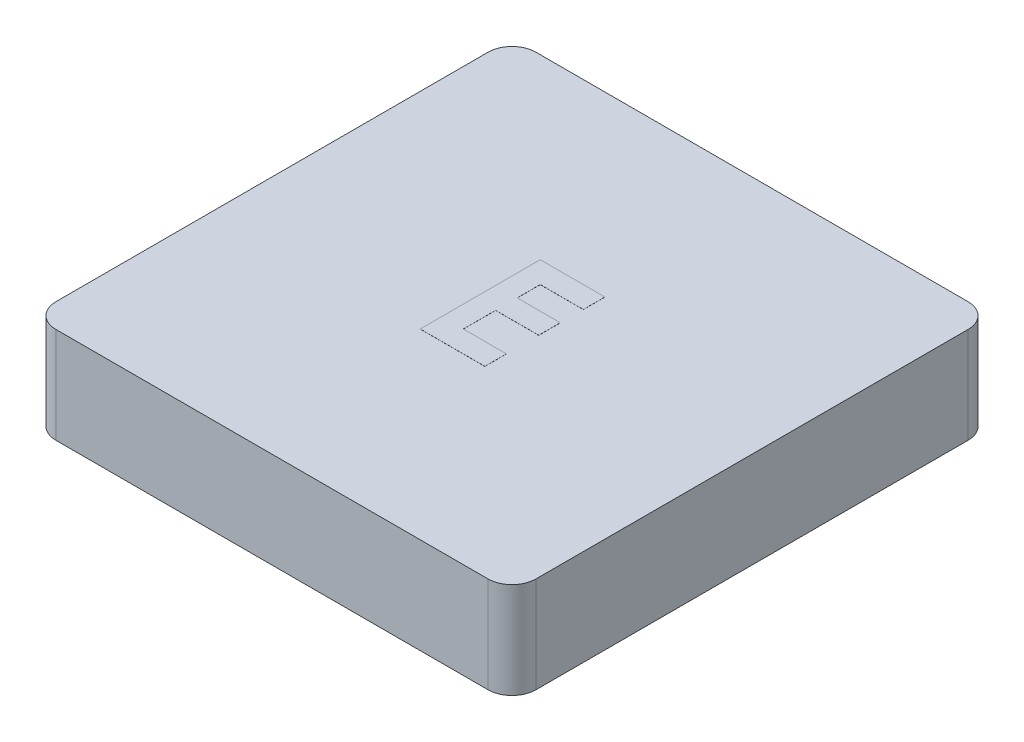
SolidWorks part; units mm, degrees
ref_plane "Front Plane" through (0, 0, 0) normal (0, 0, 1) x (1, 0, 0)
ref_plane "Top Plane" through (0, 0, 0) normal (0, 1, 0) x (1, 0, 0)
ref_plane "Right Plane" through (0, 0, 0) normal (1, 0, 0) x (0, 0, -1)
sketch "Sketch1" plane through (0, 0, 0) normal (0, 1, 0) x (1, 0, 0)
  line L0 (0, 0) -> (12.7, 0)
  line L1 (12.7, 0) -> (12.7, 12.7)
  line L2 (12.7, 12.7) -> (0, 12.7)
  line L3 (0, 12.7) -> (0, 0)
  dimension "D1" = 12.7
  dimension "D2" = 12.7
extrude "Boss-Extrude1" add sketch "Sketch1" along normal blind 2.54
fillet "Fillet1" radius 0.635 4 edges at (0, 1.27, -12.7) (12.7, 1.27, -12.7) (12.7, 1.27, 0) (0, 1.27, 0)
shell "Shell1" thickness 0.635 removed face at (6.35, 0, -6.35)
sketch "Sketch2" plane through (0, 1.905, 0) normal (0, -1, 0) x (-1, 0, 0)
  line L0 (-0.635, 6.35) -> (-12.065, 6.35) construction
  line L1 (-0.635, 12.065) -> (-0.635, 0.635) construction
  line L2 (-12.065, 0.635) -> (-12.065, 12.065) construction
  line L3 (-6.35, 0.635) -> (-6.35, 12.065) construction
  line L4 (-0.635, 0.635) -> (-12.065, 0.635) construction
  line L5 (-12.065, 12.065) -> (-0.635, 12.065) construction
  circle A0 centre (-6.35, 6.35) radius 2.54
  dimension "D1" = 5.08
extrude "Boss-Extrude2" add sketch "Sketch2" along normal up to surface (1.905 mm away) up to face at (6.35, 0, -6.35)
sketch "Sketch3" plane through (0, 2.54, 0) normal (0, 1, 0) x (1, 0, 0)
  line L0 (0, 12.065) -> (0, 0.635) construction
  line L1 (0.635, 0) -> (12.065, 0) construction
  text T0 "<b>E</b>"
  point P1 (0, 0)
  dimension "D1" = 5.08
  dimension "D2" = 4.826
extrude "Boss-Extrude3" add sketch "Sketch3" along normal blind 0.0025
